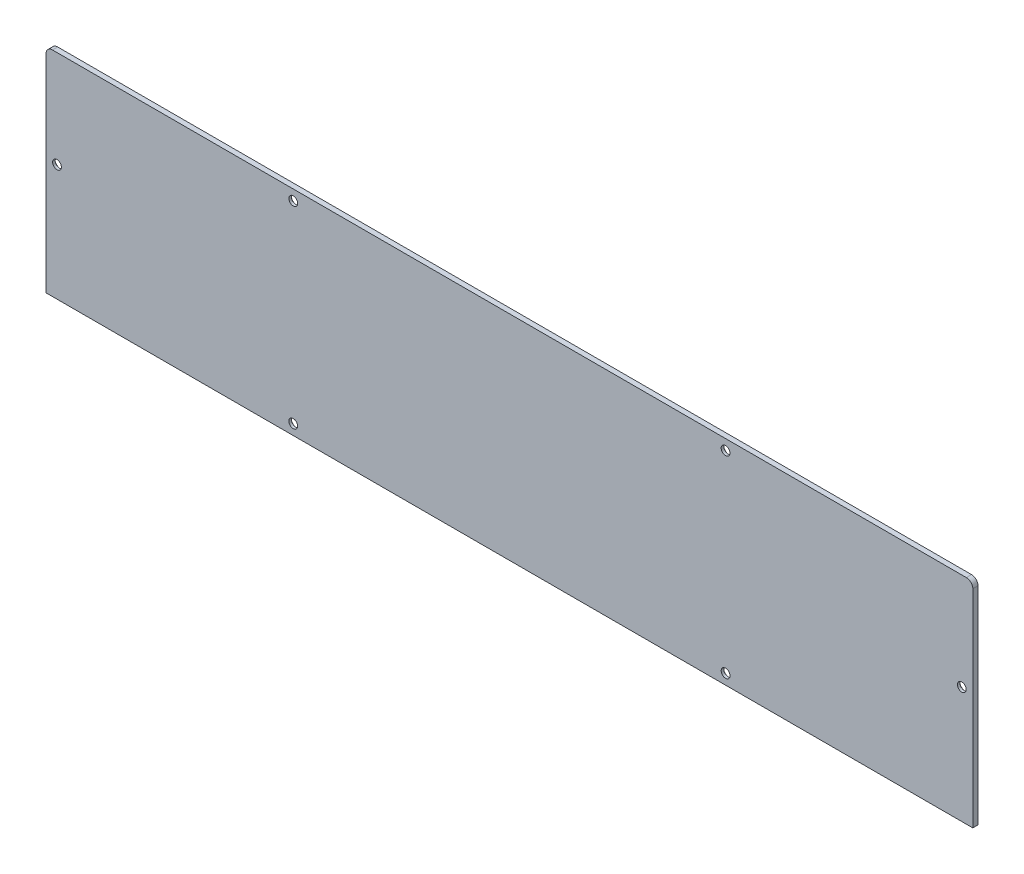
SolidWorks part; units mm, degrees
material "6061 合金"
ref_plane "前视基准面" through (0, 0, 0) normal (0, 0, 1) x (1, 0, 0)
ref_plane "上视基准面" through (0, 0, 0) normal (0, 1, 0) x (1, 0, 0)
ref_plane "右视基准面" through (0, 0, 0) normal (1, 0, 0) x (0, 0, -1)
sketch "草图1" plane through (0, 0, 222.7245) normal (0, 0, -1) x (-1, 0, 0)
  line L0 (282.7502, -10) -> (-76.2519, -10) construction
  line L1 (-76.2519, 70) -> (-76.2519, -2.5) construction
  line L2 (282.7502, -8.05) -> (282.7502, 70) construction
  line L4 (-76.2519, -10) -> (282.7502, -10)
  line L5 (282.7502, 70) -> (282.7502, -10)
  line L6 (279.7502, 73) -> (-73.2519, 73)
  line L7 (-76.2519, -10) -> (-76.2519, 70)
  arc A2 (282.7502, 70) -> (279.7502, 73) centre (279.7502, 70) ccw
  arc A3 (-73.2519, 73) -> (-76.2519, 70) centre (-73.2519, 70) ccw
  arc A4 (-73.2519, 73) -> (-76.2519, 70) centre (-73.2519, 70) ccw construction
  arc A5 (282.7502, 70) -> (279.7502, 73) centre (279.7502, 70) ccw construction
extrude "凸台-拉伸1" add sketch "草图1" along normal blind 2
sketch "草图2" plane through (0, 0, 220.7245) normal (0, 0, 1) x (1, 0, 0)
  line L0 (71.5019, 35) -> (71.5019, 68.5) construction
  line L1 (71.5019, 68.5) -> (-19.7492, 68.5) construction
  line L2 (-19.7492, 68.5) -> (-186.7492, 68.5) construction
  line L3 (-186.7492, 68.5) -> (-278.0002, 68.5) construction
  line L4 (-278.0002, 68.5) -> (-278.0002, 35) construction
  circle A1 centre (-19.7492, 68.5) radius 1.25 construction
  circle A4 centre (-278.0002, 35) radius 1.25
  circle A5 centre (-186.7492, 68.5) radius 1.25
  circle A6 centre (-19.7492, 68.5) radius 1.0541
  circle A7 centre (71.5019, 35) radius 1.25
  circle A11 centre (-278.0002, 35) radius 1.0974 construction
  circle A14 centre (71.5019, 35) radius 1.25 construction
hole_wizard "打孔尺寸(%根据)内六角圆柱头螺钉的类型2" positions "3D草图1" profile "草图3" counterbore size "M3" standard "GB"
sketch3d "3D草图1"
  point P0 (71.5019, 35, 220.7245)
  point P3 (-19.7492, 68.5, 220.7245)
  point P6 (-186.7492, 68.5, 220.7245)
  point P9 (-278.0002, 35, 220.7245)
sketch "草图3" plane through (71.5019, 35, 220.7245) normal (1, 0, 0) x (0, 1, 0)
  line L0 (0, 0) -> (0, 8.5215)
  line L1 (0, 8.5215) -> (1.7, 7.5)
  line L2 (1.7, 7.5) -> (1.7, 1)
  line L3 (1.7, 1) -> (3, 1)
  line L4 (3, 1) -> (3, 0)
  line L5 (3, 0) -> (0, 0)
  line L10 (0, 8.5215) -> (-1.7, 7.5) construction
  line L11 (0, -6.35) -> (0, 107.95) construction
  dimension "孔直径" = 3.4
  dimension "孔深度" = 7.5
  dimension "柱形沉头孔直径" = 6
  dimension "柱形沉头孔深度" = 1
  dimension "导头角度" = 118
sketch "草图4" plane through (0, 0, 220.7245) normal (0, 0, -1) x (-1, 0, 0)
  line L4 (-76.2519, 70) -> (-76.2519, -10)
  line L5 (-76.2519, -10) -> (282.7502, -10)
  line L6 (282.7502, -10) -> (282.7502, 70)
  line L7 (279.7502, 73) -> (-73.2519, 73)
  line L8 (-76.2519, 70) -> (-76.2519, -10)
  line L10 (282.7502, -10) -> (282.7502, 70)
  line L11 (279.7502, 73) -> (-73.2519, 73)
  line L13 (282.2502, -10) -> (282.2502, 70)
  line L14 (279.7502, 72.5) -> (-73.2519, 72.5)
  line L15 (-75.7519, 70) -> (-75.7519, -10)
  line L16 (282.2502, -10) -> (282.7502, -10)
  line L17 (-76.2519, -10) -> (-75.7519, -10)
  arc A2 (282.7502, 70) -> (279.7502, 73) centre (279.7502, 70) ccw
  arc A3 (-73.2519, 73) -> (-76.2519, 70) centre (-73.2519, 70) ccw
  arc A4 (282.7502, 70) -> (279.7502, 73) centre (279.7502, 70) ccw
  arc A5 (-73.2519, 73) -> (-76.2519, 70) centre (-73.2519, 70) ccw
  arc A6 (282.2502, 70) -> (279.7502, 72.5) centre (279.7502, 70) ccw
  arc A8 (-73.2519, 72.5) -> (-75.7519, 70) centre (-73.2519, 70) ccw
  dimension "D1" = 0
  dimension "D3" = 0.5
extrude "切除-拉伸1" cut sketch "草图4" against normal through all
hole_wizard "打孔尺寸(%根据)内六角圆柱头螺钉的类型2" positions "3D草图2" profile "草图5" counterbore size "M3" standard "GB"
sketch3d "3D草图2"
  point P0 (-19.7492, -6, 195.7245)
  point P3 (-186.7492, -6, 195.7245)
sketch "草图5" plane through (-19.7492, -6, 220.7245) normal (1, 0, 0) x (0, 1, 0)
  line L0 (0, 0) -> (0, 20.5215)
  line L1 (0, 20.5215) -> (1.7, 19.5)
  line L2 (1.7, 19.5) -> (1.7, 1)
  line L3 (1.7, 1) -> (3, 1)
  line L4 (3, 1) -> (3, 0)
  line L5 (3, 0) -> (0, 0)
  line L6 (0, 20.5215) -> (-1.7, 19.5) construction
  line L7 (0, -6.35) -> (0, 107.95) construction
  dimension "孔直径" = 3.4
  dimension "孔深度" = 19.5
  dimension "柱形沉头孔直径" = 6
  dimension "柱形沉头孔深度" = 1
  dimension "导头角度" = 118
